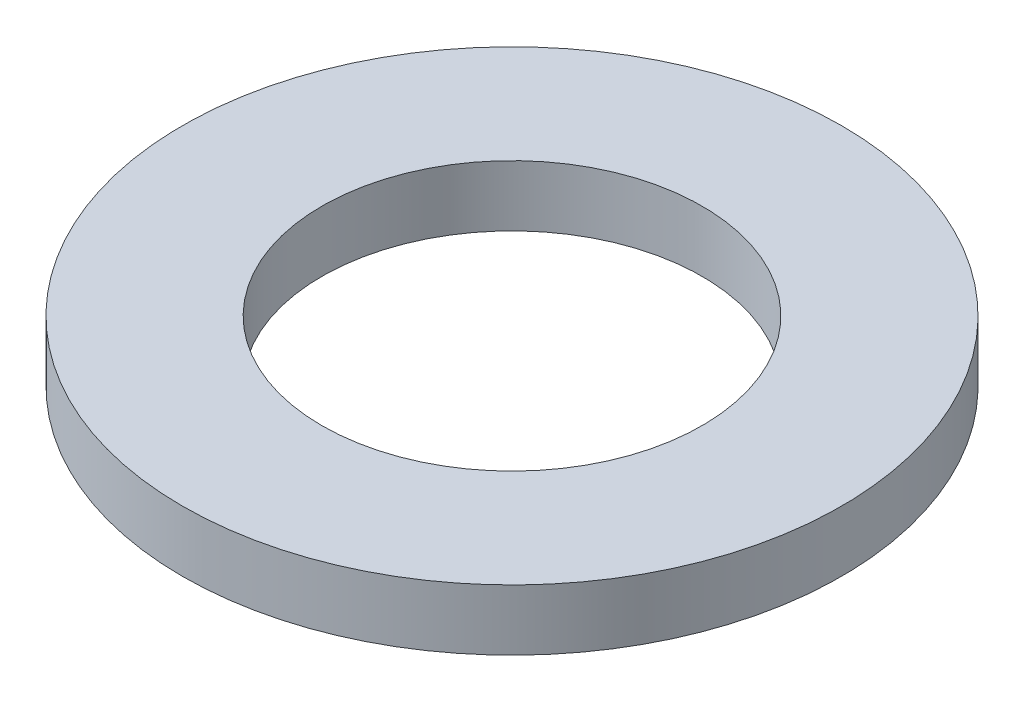
SolidWorks part; units mm, degrees
ref_plane "Front Plane" through (0, 0, 0) normal (0, 0, 1) x (1, 0, 0)
ref_plane "Top Plane" through (0, 0, 0) normal (0, 1, 0) x (1, 0, 0)
ref_plane "Right Plane" through (0, 0, 0) normal (1, 0, 0) x (0, 0, -1)
sketch "Sketch1" plane through (0, 0, 0) normal (0, 1, 0) x (1, 0, 0)
  circle A0 centre (0, 0) radius 65
  dimension "FLANGE_OD" = 130
extrude "Boss-Extrude1" add sketch "Sketch1" along normal blind 12
sketch "Sketch2" plane through (0, 0, 0) normal (0, 1, 0) x (1, 0, 0)
  circle A0 centre (0, 0) radius 37.5
  dimension "BORE_D" = 75
extrude "Cut-Extrude1" cut sketch "Sketch2" along normal through all
sketch "Sketch3" plane through (0, 12, 0) normal (0, 1, 0) x (1, 0, 0)
  circle A0 centre (0, 0) radius 24.2301 construction
  circle A1 centre (-24.2301, 0) radius 1.6762
  dimension "BOLT_D" = 3.3523
  dimension "BOLT_PCD" = 48.4603
extrude "Cut-Extrude2" cut sketch "Sketch3" against normal blind 7.9218 rebuild error yes
pattern_circular "CirPattern1" count 6 over 360 rebuild error yes
